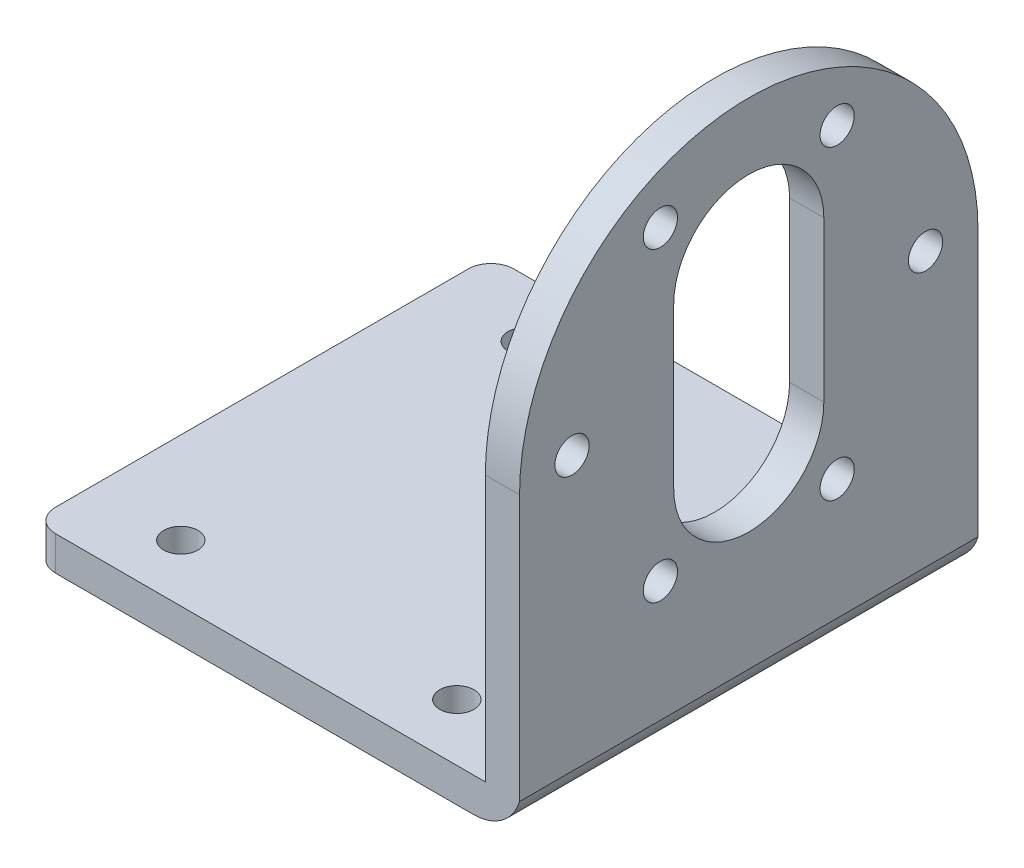
SolidWorks part; units mm, degrees
ref_plane "Front Plane" through (0, 0, 0) normal (0, 0, 1) x (1, 0, 0)
ref_plane "Top Plane" through (0, 0, 0) normal (0, 1, 0) x (1, 0, 0)
ref_plane "Right Plane" through (0, 0, 0) normal (1, 0, 0) x (0, 0, -1)
sketch "Sketch1" plane through (0, 0, 0) normal (0, 0, 1) x (1, 0, 0)
  line L6 (-4.0423, 0) -> (-42.7, 0)
  line L7 (-42.7, 0) -> (-42.7, 3)
  line L8 (0, 3) -> (0, 46.4)
  line L9 (0, 46.4) -> (-3, 46.4)
  line L10 (-3, 46.4) -> (-3, 3)
  line L11 (-3, 3) -> (-42.7, 3)
  arc A0 (-4.0423, 0) -> (0, 3) centre (-4.0423, 4.2233) ccw
  dimension "D1" = 3
  dimension "D2" = 3
  dimension "D3" = 42.7
  dimension "D4" = 46.4
extrude "Boss-Extrude1" add sketch "Sketch1" along normal blind 40.2
sketch "Sketch2" plane through (0, 0, 0) normal (1, 0, 0) x (0, 0, -1)
  line L0 (-20.1, 46.4) -> (-20.1, 9.7018) construction
  line L1 (-40.2, 46.4) -> (0, 46.4) construction
  line L2 (-40.2, 3) -> (0, 3) construction
  line L3 (-40.2, 46.4) -> (-40.2, 26.3)
  line L5 (-40.2, 46.4) -> (-20.1, 46.4)
  line L7 (0, 3) -> (0, 46.4) construction
  line L8 (0, 46.4) -> (-20.1, 46.4)
  line L9 (-20.1, 3) -> (-20.1, 0) construction
  line L10 (0, 0) -> (0, 20) construction
  line L14 (-40.2, 3) -> (-40.2, 46.4) construction
  line L15 (0, 46.4) -> (0, 26.3)
  arc A11 (0, 26.3) -> (-40.2, 26.3) centre (-20.1, 26.3) ccw
extrude "Cut-Extrude1" cut sketch "Sketch2" against normal blind 40
sketch "Sketch7" plane through (0, 0, 0) normal (1, 0, 0) x (0, 0, -1)
  line L0 (-20.1, 46.4) -> (-20.1, 3) construction
  line L1 (-40.2, 3) -> (0, 3) construction
  line L2 (-26.68, 34) -> (-26.68, 20)
  line L4 (-13.52, 34) -> (-13.52, 20)
  arc A1 (-26.68, 20) -> (-13.52, 20) centre (-20.1, 20) ccw
  arc A2 (-13.52, 34) -> (-26.68, 34) centre (-20.1, 34) ccw
  arc A3 (0, 26.3) -> (-40.2, 26.3) centre (-20.1, 26.3) ccw construction
  dimension "D1" = 13.16
  dimension "D2" = 20
  dimension "D3" = 34
extrude "Cut-Extrude4" cut sketch "Sketch7" against normal blind 40
sketch "Sketch8" plane through (0, 0, 0) normal (1, 0, 0) x (0, 0, -1)
  line L0 (-20.1, 13.42) -> (-20.1, 40.58) construction
  line L1 (-35.6, 27) -> (-4.6, 27) construction
  arc A0 (-26.68, 20) -> (-13.52, 20) centre (-20.1, 20) ccw construction
  arc A1 (-13.52, 34) -> (-26.68, 34) centre (-20.1, 34) ccw construction
  circle A2 centre (-35.6, 27) radius 1.5
  circle A3 centre (-27.85, 40.4234) radius 1.5
  circle A4 centre (-12.35, 40.4234) radius 1.5
  circle A5 centre (-4.6, 27) radius 1.5
  circle A6 centre (-12.35, 13.5766) radius 1.5
  circle A7 centre (-27.85, 13.5766) radius 1.5
  point P13 (-20.1, 27)
  point P25 (-20.1, 27)
  dimension "D2" = 3
  dimension "D1" = 31
  dimension "D3" = 6
extrude "Cut-Extrude5" cut sketch "Sketch8" against normal blind 40
sketch "Sketch9" plane through (0, 3, 0) normal (0, 1, 0) x (1, 0, 0)
  line L1 (-3, 0) -> (-42.7, 0) construction
  circle A0 centre (-10.5, -35.25) radius 1.75
  circle A1 centre (-10.5, -5.25) radius 1.75
  circle A2 centre (-34.7, -35.25) radius 1.75
  circle A3 centre (-34.7, -5.25) radius 1.75
  dimension "D1" = 10.5
  dimension "D4" = 3.5
  dimension "D5" = 24.2
  dimension "D2" = 30
  dimension "D3" = 5.25
fillet "Fillet2" radius 2 2 edges at (-42.7, 1.5, 0) (-42.7, 1.5, 40.2)
sketch "Sketch5" plane through (0, 3, 0) normal (0, 1, 0) x (1, 0, 0)
  line L0 (-3, 0) -> (-40.7, 0) construction
  line L2 (-3, -40.2) -> (-40.7, -40.2) construction
  line L3 (-42.7, -38.2) -> (-42.7, -2) construction
  circle A0 centre (-10.5, -5) radius 1.5
  circle A1 centre (-10.5, -35.2) radius 1.5
  circle A2 centre (-34.7, -35.2) radius 1.5
  circle A3 centre (-34.7, -5) radius 1.5
  dimension "D1" = 5
  dimension "D2" = 5
  dimension "D4" = 3
  dimension "D5" = 8
  dimension "D8" = 10.5
extrude "Cut-Extrude6" cut sketch "Sketch5" against normal through all
